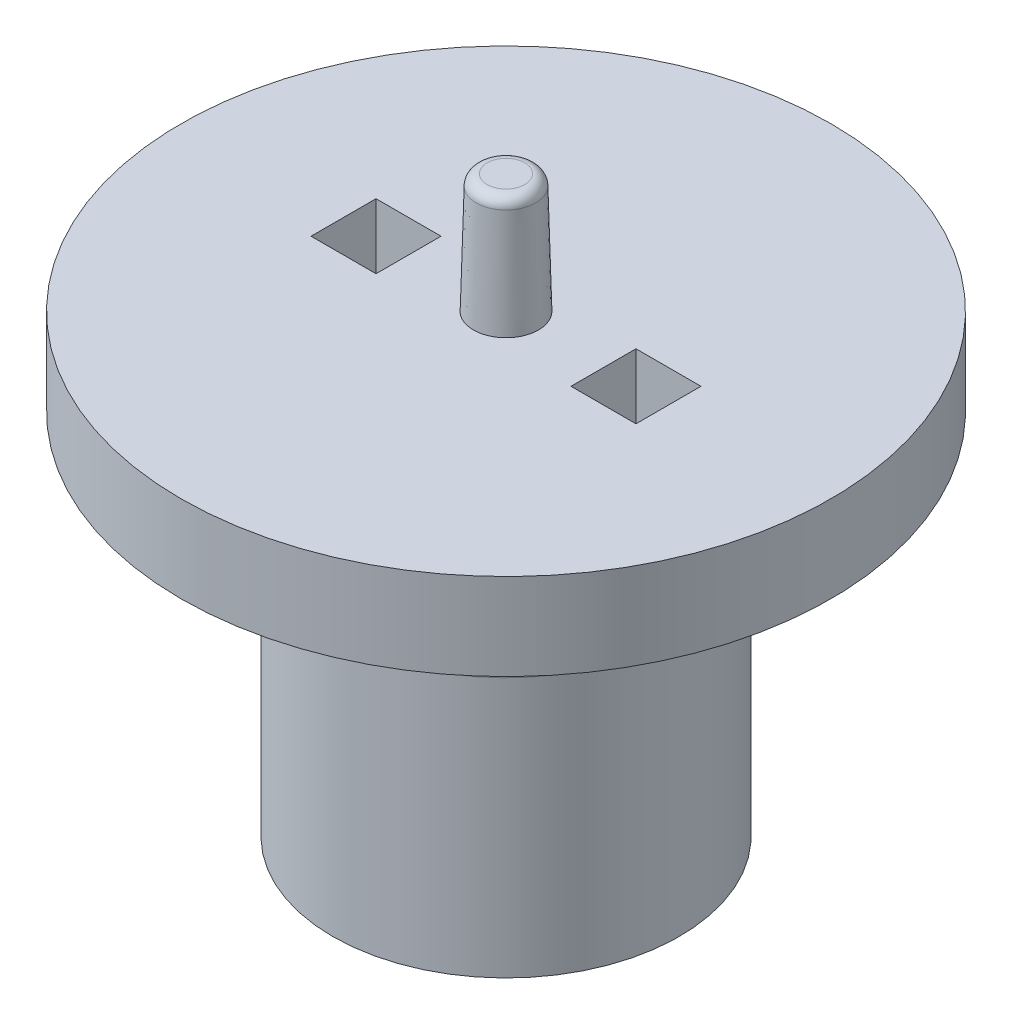
SolidWorks part; units mm, degrees
ref_plane "Front Plane" through (0, 0, 0) normal (0, 0, 1) x (1, 0, 0)
ref_plane "Top Plane" through (0, 0, 0) normal (0, 1, 0) x (1, 0, 0)
ref_plane "Right Plane" through (0, 0, 0) normal (1, 0, 0) x (0, 0, -1)
sketch "Sketch1" plane through (0, 0, 0) normal (0, 1, 0) x (1, 0, 0)
  circle A0 centre (0, 0) radius 8
  circle A1 centre (0, 0) radius 2.575
  dimension "D1" = 16
  dimension "D2" = 5.15
extrude "Boss-Extrude1" add sketch "Sketch1" along normal blind 15
sketch "Sketch2" plane through (0, 0, 0) normal (0, 0, 1) x (1, 0, 0)
  line L1 (0, 7.5) -> (0, 15) construction
  line L2 (0, 7.5) -> (0, 0) construction
  circle A0 centre (0, 7.5) radius 1.25
  dimension "D1" = 2.5
extrude "Cut-Extrude1" cut sketch "Sketch2" against normal through all contours A0
ref_plane "Plane1" through (0, 0, -8) normal (0, 0, -1) x (-1, 0, 0)
sketch "Sketch12" plane through (0, 15, 0) normal (0, 1, 0) x (1, 0, 0)
  circle A0 centre (0, 0) radius 8
  circle A1 centre (0, 0) radius 8 construction
extrude "Boss-Extrude3" add sketch "Sketch12" along normal blind 2
sketch "Sketch10" plane through (0, 17, 0) normal (0, 1, 0) x (1, 0, 0)
  circle A0 centre (0, 0) radius 7.5
sketch "Sketch11" plane through (0, 17, 0) normal (0, 1, 0) x (1, 0, 0)
  line L0 (6, 0) -> (0, 0) construction
  line L1 (-7.5, 1.5) -> (-4.5, 1.5)
  line L2 (-7.5, 1.5) -> (-7.5, -1.5)
  line L3 (-7.5, -1.5) -> (-4.5, -1.5)
  line L4 (-4.5, 1.5) -> (-4.5, -1.5)
  line L5 (-7.5, 1.5) -> (-4.5, -1.5) construction
  line L6 (-7.5, -1.5) -> (-4.5, 1.5) construction
  line L7 (4.5, 1.5) -> (7.5, 1.5)
  line L8 (4.5, 1.5) -> (4.5, -1.5)
  line L9 (4.5, -1.5) -> (7.5, -1.5)
  line L10 (7.5, 1.5) -> (7.5, -1.5)
  line L11 (4.5, 1.5) -> (7.5, -1.5) construction
  line L12 (4.5, -1.5) -> (7.5, 1.5) construction
  line L13 (0, 0) -> (-6, 0) construction
  circle A0 centre (0, 0) radius 15
  point P0 (-6, 0)
  point P5 (6, 0)
  dimension "D4" = 30
  dimension "D1" = 3
  dimension "D2" = 3
  dimension "D3" = 6
  dimension "D5" = 3
extrude "Boss-Extrude2" add sketch "Sketch11" along normal blind 4
sketch "Sketch13" plane through (0, 21, 0) normal (0, 1, 0) x (1, 0, 0)
  circle A0 centre (0, 0) radius 1.5
  dimension "D1" = 3
extrude "Boss-Extrude4" add sketch "Sketch13" along normal blind 5.5 draft 1.5
fillet "Fillet2" radius 0.5 1 edges at (0, 26.5, 1.356)
fillet "Fillet4" radius 5 1 edges at (0, 17, 8)
